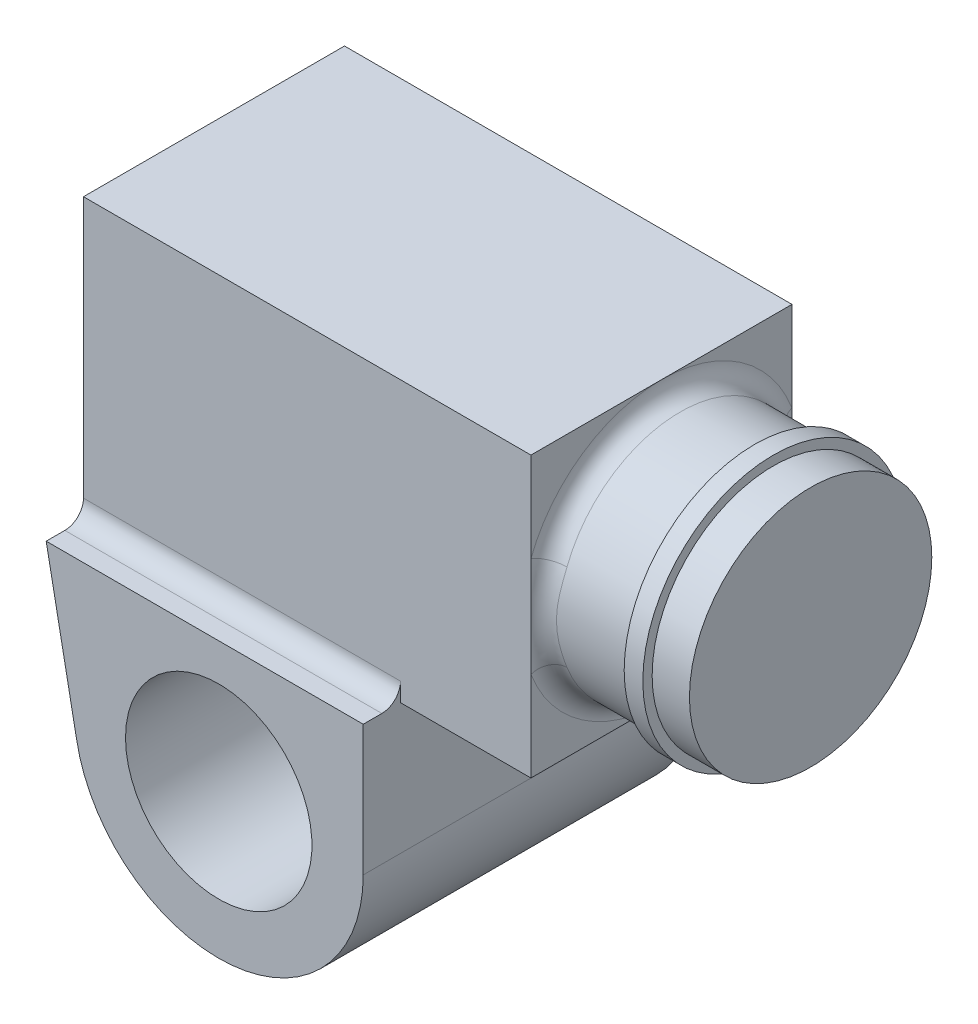
SolidWorks part; units mm, degrees
material "201 Annealed Stainless Steel (SS)"
ref_plane "Front Plane" through (0, 0, 0) normal (0, 0, 1) x (1, 0, 0)
ref_plane "Top Plane" through (0, 0, 0) normal (0, 1, 0) x (1, 0, 0)
ref_plane "Right Plane" through (0, 0, 0) normal (1, 0, 0) x (0, 0, -1)
sketch "Sketch1" plane through (0, 0, 0) normal (1, 0, 0) x (0, 0, -1)
  line L1 (-70, 75) -> (70, 75)
  line L2 (-70, 75) -> (-70, -75)
  line L3 (-70, -75) -> (70, -75)
  line L4 (70, 75) -> (70, -75)
  line L5 (-70, 75) -> (70, -75) construction
  line L6 (-70, -75) -> (70, 75) construction
  point P0 (0, 0)
  dimension "D1" = 150
  dimension "D2" = 140
extrude "Boss-Extrude1" add sketch "Sketch1" along normal blind 240
sketch "Sketch2" plane through (240, 0, 0) normal (1, 0, 0) x (0, 0, -1)
  circle A0 centre (0, 0) radius 65
  dimension "D1" = 130
extrude "Boss-Extrude2" add sketch "Sketch2" along normal blind 50
sketch "Sketch3" plane through (290, 0, 0) normal (1, 0, 0) x (0, 0, -1)
  circle A0 centre (0, 0) radius 70
  dimension "D1" = 140
extrude "Boss-Extrude3" add sketch "Sketch3" along normal blind 10
sketch "Sketch4" plane through (0, 0, 0) normal (0, 0, 1) x (1, 0, 0)
  line L0 (0, -75) -> (16.2188, -158.4383)
  line L1 (0, 75) -> (0, -75) construction
  line L2 (170.0448, -145) -> (170.0448, -75)
  line L3 (240, -75) -> (0, -75) construction
  line L5 (0, -75) -> (170.0448, -75)
  arc A0 (16.2188, -158.4383) -> (170.0448, -145) centre (92.5448, -145) ccw
  circle A1 centre (92.5448, -145) radius 50
  dimension "D1" = 155
  dimension "D2" = 100
  dimension "D3" = 191
  dimension "D4" = 85
  dimension "D5" = 70
extrude "Boss-Extrude4" add sketch "Sketch4" along normal mid plane 180
fillet "Fillet1" radius 10 3 edges at (85.0224, -75, 70) (240, 0, -65) (85.0224, -75, -70)
sketch "Sketch5" plane through (300, 0, 0) normal (1, 0, 0) x (0, 0, -1)
  circle A0 centre (0, 0) radius 65
  dimension "D1" = 130
extrude "Boss-Extrude5" add sketch "Sketch5" along normal blind 20
sketch "Sketch6" plane through (0, 0, 0) normal (0, 0, 1) x (1, 0, 0)
  line L0 (520, 75) -> (320, 75)
  line L1 (320, 75) -> (320, -75)
  line L2 (320, -75) -> (520, -75)
  line L3 (320, -65) -> (320, 65) construction
  arc A0 (520, -75) -> (520, 75) centre (520, 0) ccw
  dimension "D1" = 150
  dimension "D2" = 200
extrude "Boss-Extrude7" add sketch "Sketch6" along normal mid plane 140
sketch "Sketch8" plane through (0, 0, 0) normal (0, 0, 1) x (1, 0, 0)
  line L0 (520, 75) -> (420, 75)
  line L1 (520, 75) -> (320, 75) construction
  line L2 (420, 75) -> (420, -75)
  line L3 (320, -75) -> (520, -75) construction
  line L4 (420, -75) -> (520, -75)
  arc A0 (520, -75) -> (520, 75) centre (520, 0) ccw construction
  arc A1 (520, -75) -> (520, 75) centre (520, 0) ccw
extrude "Cut-Extrude1" cut sketch "Sketch8" against normal mid plane 100
sketch "Sketch9" plane through (0, 0, -50) normal (0, 0, 1) x (1, 0, 0)
  circle A0 centre (520, 0) radius 50
  dimension "D1" = 100
extrude "Boss-Extrude8" add sketch "Sketch9" along normal blind 100
sketch "Sketch10" plane through (320, 0, 0) normal (-1, 0, 0) x (0, 0, 1)
  line L1 (-186.2667, 136.2774) -> (171.8406, 136.2774)
  line L2 (-186.2667, 136.2774) -> (-186.2667, -255.7737)
  line L3 (-186.2667, -255.7737) -> (171.8406, -255.7737)
  line L4 (171.8406, 136.2774) -> (171.8406, -255.7737)
  line L5 (-7.2131, -255.7737) -> (-7.2131, 136.2774) construction
  line L6 (-186.2667, -59.7482) -> (171.8406, -59.7482) construction
  point P0 (-7.2131, -59.7482)
extrude "Cut-Extrude2" cut sketch "Sketch10" against normal through all
sketch "Sketch12" plane through (0, 0, 0) normal (0, 0, 1) x (1, 0, 0)
  line L0 (320, 0) -> (639.4574, 0) construction
  line L1 (320, -65) -> (320, 65) construction
  point P2 (0, 0)
